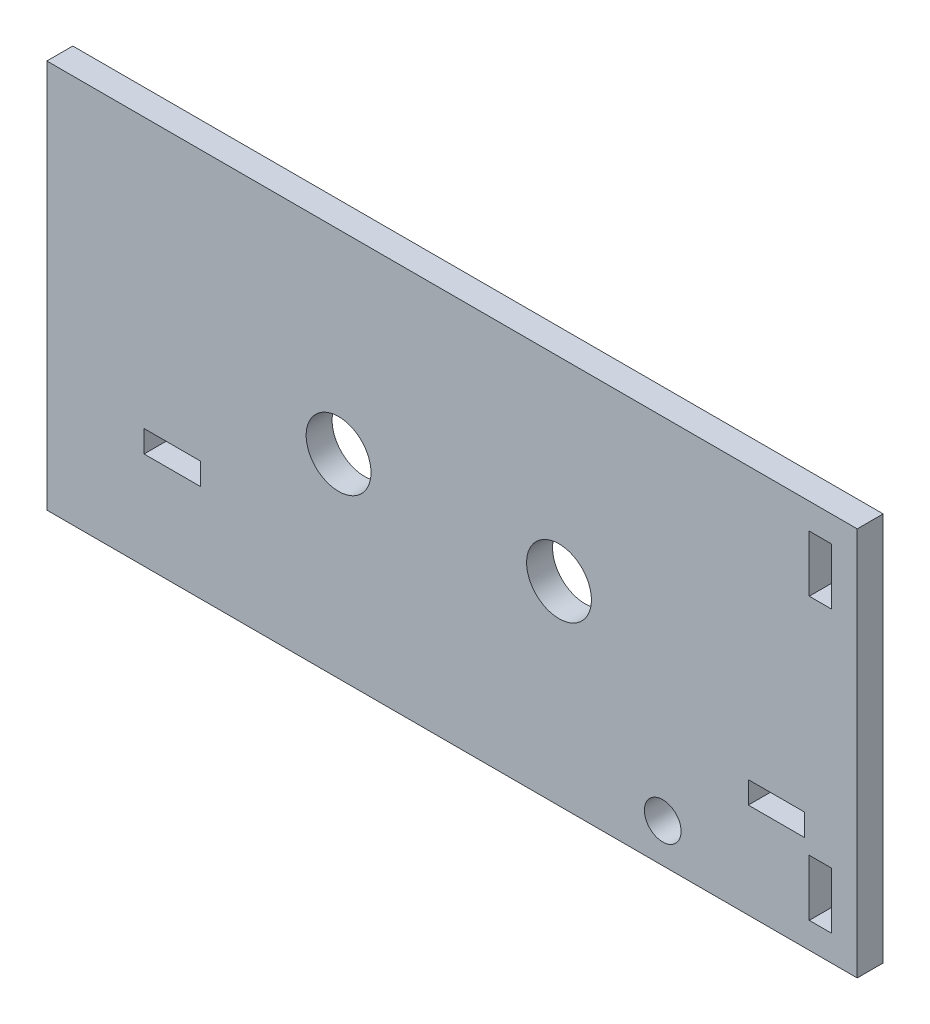
SolidWorks part; units mm, degrees
ref_plane "Front Plane" through (0, 0, 0) normal (0, 0, 1) x (1, 0, 0)
ref_plane "Top Plane" through (0, 0, 0) normal (0, 1, 0) x (1, 0, 0)
ref_plane "Right Plane" through (0, 0, 0) normal (1, 0, 0) x (0, 0, -1)
sketch "Sketch1" plane through (0, 0, 0) normal (0, 0, 1) x (1, 0, 0)
  line L1 (-79, -18.3961) -> (42, -18.3961)
  line L2 (-79, -18.3961) -> (-79, 41.6039)
  line L3 (-79, 41.6039) -> (42, 41.6039)
  line L4 (42, -18.3961) -> (42, 41.6039)
  line L5 (-64, 0.0039) -> (-55.3, 0.0039)
  line L6 (-64, 0.0039) -> (-64, -3.3961)
  line L7 (-64, -3.3961) -> (-55.3, -3.3961)
  line L8 (-55.3, 0.0039) -> (-55.3, -3.3961)
  line L9 (29.2, -0.2961) -> (37.9, -0.2961)
  line L10 (29.2, -0.2961) -> (29.2, -3.6961)
  line L11 (29.2, -3.6961) -> (37.9, -3.6961)
  line L12 (37.9, -0.2961) -> (37.9, -3.6961)
  circle A2 centre (-34, 11.6039) radius 5
  circle A3 centre (0, 11.6039) radius 5
  circle A4 centre (16, -12.3961) radius 2.83
  point P1 (0, 0)
  point P6 (-79, 11.6039)
  point P7 (42, 11.6039)
  point P22 (-55.3, -1.6961)
  dimension "D3" = 0
  dimension "D4" = 121
  dimension "D5" = 45
  dimension "D6" = 8.7
  dimension "D7" = 34
  dimension "D10" = 10
  dimension "D12" = 95
  dimension "D13" = 6
  dimension "D14" = 5.66
  dimension "D15" = 42
  dimension "D2" = 60
  dimension "D8" = 3.4
  dimension "D9" = 15
  dimension "D11" = 15
  dimension "D16" = 84.5
extrude "Boss-Extrude1" add sketch "Sketch1" along normal blind 4
sketch "Sketch2" plane through (0, 0, 0) normal (0, 0, 1) x (1, 0, 0)
  line L0 (42, 41.6039) -> (46, 41.6039)
  line L1 (46, 41.6039) -> (46, -18.3961)
  line L2 (46, -18.3961) -> (42, -18.3961)
  line L13 (-79, -18.3961) -> (42, -18.3961) construction
  line L14 (42, -18.3961) -> (42, 41.6039)
  dimension "D1" = 4
extrude "Boss-Extrude2" add sketch "Sketch2" along normal blind 4
sketch "Sketch3" plane through (0, 0, 0) normal (0, 0, 1) x (1, 0, 0)
  line L0 (46, -18.3961) -> (46, 41.6039) construction
  line L1 (38.6, 37.6039) -> (42, 37.6039)
  line L2 (38.6, 37.6039) -> (38.6, 28.9039)
  line L3 (38.6, 28.9039) -> (42, 28.9039)
  line L4 (42, 37.6039) -> (42, 28.9039)
  line L5 (38.6, -5.6961) -> (42, -5.6961)
  line L6 (38.6, -5.6961) -> (38.6, -14.3961)
  line L7 (38.6, -14.3961) -> (42, -14.3961)
  line L8 (42, -5.6961) -> (42, -14.3961)
  line L9 (46, 41.6039) -> (-79, 41.6039) construction
  line L10 (-79, -18.3961) -> (46, -18.3961) construction
  dimension "D1" = 4
  dimension "D2" = 3.4
  dimension "D3" = 8.7
  dimension "D4" = 4
  dimension "D5" = 4
extrude "Cut-Extrude2" cut sketch "Sketch3" along normal through all both
equation "\"padding\"=4"
equation "\"hole_width\"=3.4"
equation "\"hole_height\"=8.7"
equation "\"D1@Sketch3\"=\"padding\""
equation "\"D2@Sketch3\"=\"hole_width\""
equation "\"D3@Sketch3\"=\"hole_height\""
equation "\"D4@Sketch3\"=\"padding\""
equation "\"D5@Sketch3\"=\"padding\""
